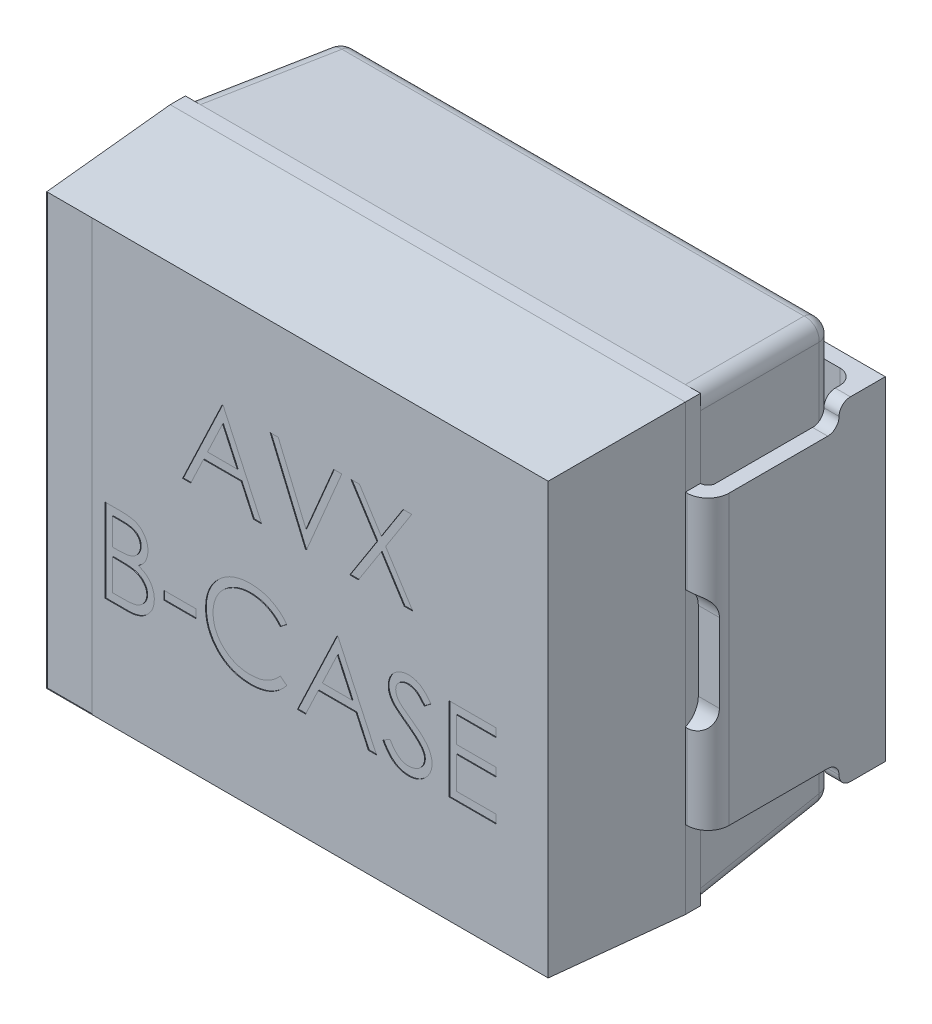
SolidWorks part; units mm, degrees
ref_plane "Front Plane" through (0, 0, 0) normal (0, 0, 1) x (1, 0, 0)
ref_plane "Top Plane" through (0, 0, 0) normal (0, 1, 0) x (1, 0, 0)
ref_plane "Right Plane" through (0, 0, 0) normal (1, 0, 0) x (0, 0, -1)
sketch "Sketch1" plane through (0, 0, 0) normal (0, 0, 1) x (1, 0, 0)
  line L1 (-1.7, -1.465) -> (-1.7, 1.465)
  line L2 (-1.7, -1.465) -> (1.7, -1.465)
  line L3 (1.7, -1.465) -> (1.7, 1.465)
  line L4 (-1.7, 1.465) -> (1.7, 1.465)
  dimension "D1" = 3.4
  dimension "D2" = 2.93
  dimension "D3" = 1.465
  dimension "D4" = 1.7
extrude "Boss-Extrude1" add sketch "Sketch1" along normal blind 0.95 from offset 0.12
ref_plane "Plane1" through (0, 0, 1.07) normal (0, 0, 1) x (1, 0, 0)
ref_plane "Plane2" through (0, 0, 1.17) normal (0, 0, 1) x (1, 0, 0)
sketch "Sketch2" plane through (0, 0, 1.07) normal (0, 0, 1) x (1, 0, 0)
  line L1 (-1.7, -1.465) -> (-1.7, 1.465)
  line L2 (-1.7, -1.465) -> (1.7, -1.465)
  line L3 (1.7, -1.465) -> (1.7, 1.465)
  line L4 (-1.7, 1.465) -> (1.7, 1.465)
  dimension "D1" = 1.7
  dimension "D2" = 2.93
  dimension "D3" = 1.465
  dimension "D4" = 3.4
sketch "Sketch3" plane through (0, 0, 1.17) normal (0, 0, 1) x (1, 0, 0)
  line L1 (-1.7, -1.465) -> (-1.7, 1.465)
  line L2 (-1.7, -1.465) -> (1.7, -1.465)
  line L3 (1.7, -1.465) -> (1.7, 1.465)
  line L4 (-1.7, 1.465) -> (1.7, 1.465)
  dimension "D1" = 1.465
  dimension "D2" = 2.93
  dimension "D3" = 1.7
  dimension "D4" = 3.4
chamfer "Chamfer3" distance 0.95 angle 5 4 edges at (0, -1.465, 0.12) (1.7, 0, 0.12) (0, 1.465, 0.12) (-1.7, 0, 0.12) first distance on face at (0, -1.465, 0.595) first distance on face at (1.7, 0, 0.595) first distance on face at (0, 1.465, 0.595) first distance on face at (-1.7, 0, 0.595)
fillet "Fillet4" radius 0.1 8 edges at (-1.6584, -1.4234, 0.595) (1.6584, -1.4234, 0.595) (1.6584, 1.4234, 0.595) (-1.6584, 1.4234, 0.595) (1.6169, 0, 0.12) (0, -1.3819, 0.12) (-1.6169, 0, 0.12) (0, 1.3819, 0.12)
extrude "Boss-Extrude2" add sketch "Sketch2" along normal blind 0.1
extrude "Boss-Extrude3" add sketch "Sketch3" along normal blind 0.86 draft 3
sketch "Sketch4" plane through (0, 0, 0) normal (0, 0, 1) x (1, 0, 0)
  line L1 (-0.7, -1.25) -> (-0.7, 1.25)
  line L2 (-0.7, -1.25) -> (0.7, -1.25)
  line L3 (0.7, -1.25) -> (0.7, 1.25)
  line L4 (-0.7, 1.25) -> (0.7, 1.25)
  dimension "D1" = 0.7
  dimension "D2" = 2.5
  dimension "D3" = 1.4
  dimension "D4" = 1.25
extrude "Boss-Extrude4" add sketch "Sketch4" along normal blind 0.1 from offset 0.02
fillet "Fillet5" radius 0.1 4 edges at (0, -1.25, 0.02) (0.7, 0, 0.02) (0, 1.25, 0.02) (-0.7, 0, 0.02)
sketch "Sketch6" plane through (0, 0, 0) normal (0, 1, 0) x (1, 0, 0)
  line L0 (-1.7, -1.17) -> (-1.7, -1.07)
  line L1 (-1.6116, -1.17) -> (1.6116, -1.17) construction
  line L2 (-1.6549, -2.03) -> (-1.7, -1.17) construction
  line L3 (-1.6116, -1.07) -> (1.6116, -1.07) construction
  line L4 (-1.7, -1.17) -> (-1.7, -1.07) construction
  line L5 (-1.7, -1.07) -> (-1.701, -1.07)
  line L6 (-1.75, -1.021) -> (-1.75, -0.2)
  line L7 (-1.65, -0.1) -> (-1.15, -0.1)
  line L8 (0, -0.02) -> (0, -2.03) construction
  line L9 (-1.15, -0.1) -> (-1.15, 0)
  line L10 (-1.15, 0) -> (-1.85, 0)
  line L11 (-1.85, 0) -> (-1.85, -1.03)
  line L12 (-1.71, -1.17) -> (-1.7, -1.17)
  line L13 (-0.6, -0.02) -> (0.6, -0.02) construction
  line L14 (1.6549, -2.03) -> (-1.6549, -2.03) construction
  line L15 (1.71, -1.17) -> (1.7, -1.17)
  line L16 (1.85, 0) -> (1.85, -1.03)
  line L17 (1.15, 0) -> (1.85, 0)
  line L18 (1.15, -0.1) -> (1.15, 0)
  line L19 (1.65, -0.1) -> (1.15, -0.1)
  line L20 (1.75, -1.021) -> (1.75, -0.2)
  line L21 (1.7, -1.07) -> (1.701, -1.07)
  line L22 (1.7, -1.17) -> (1.7, -1.07)
  arc A0 (-1.85, -1.03) -> (-1.71, -1.17) centre (-1.71, -1.03) ccw
  arc A1 (-1.701, -1.07) -> (-1.75, -1.021) centre (-1.701, -1.021) cw
  arc A2 (-1.75, -0.2) -> (-1.65, -0.1) centre (-1.65, -0.2) cw
  arc A3 (1.75, -0.2) -> (1.65, -0.1) centre (1.65, -0.2) ccw
  arc A4 (1.701, -1.07) -> (1.75, -1.021) centre (1.701, -1.021) ccw
  arc A5 (1.85, -1.03) -> (1.71, -1.17) centre (1.71, -1.03) cw
  point P15 (-1.85, -1.17)
  point P21 (-1.75, -1.07)
  point P24 (-1.75, -0.1)
  point P45 (1.75, -0.1)
  point P46 (1.75, -1.07)
  point P47 (1.85, -1.17)
  dimension "D6" = 0.14
  dimension "D7" = 0.049
  dimension "D8" = 0.1
  dimension "D1" = 0.97
  dimension "D2" = 0.15
  dimension "D3" = 0.1
  dimension "D4" = 0.1
  dimension "D5" = 0.7
extrude "Boss-Extrude5" add sketch "Sketch6" along normal mid plane 2.2
ref_plane "Plane3" through (-1.85, 0, 0) normal (-1, 0, 0) x (0, 0, 1)
sketch "Sketch7" plane through (-1.85, 0, 0) normal (-1, 0, 0) x (0, 0, 1)
  line L0 (0, 0) -> (2.03, 0) construction
  line L1 (2.03, 1.4199) -> (2.03, -1.4199) construction
  line L2 (1.17, 1.1) -> (1.17, -1.1) construction
  line L4 (1.17, 0.475) -> (0.559, 0.475)
  line L5 (1.17, 0.475) -> (1.17, -0.475)
  line L6 (1.17, -0.475) -> (0.559, -0.475)
  line L7 (0.459, 0.375) -> (0.459, -0.375)
  arc A0 (0.559, -0.475) -> (0.459, -0.375) centre (0.559, -0.375) cw
  arc A1 (0.559, 0.475) -> (0.459, 0.375) centre (0.559, 0.375) ccw
  point P16 (0.459, 0.475)
  dimension "D4" = 0.1
  dimension "D1" = 0.475
  dimension "D2" = 0.95
  dimension "D3" = 0.711
extrude "Cut-Extrude3" cut sketch "Sketch7" against normal blind 0.15
sketch "Sketch11" plane through (1.7, 0, -3.4788) normal (-1, 0, 0) x (0, 0, 1)
  line L0 (4.6488, -1.1) -> (3.7088, -1.1)
  line L1 (4.6488, -0.95) -> (4.6488, -1.1)
  line L2 (4.5088, 1.1) -> (3.4788, 1.1) construction
  line L3 (4.6488, 1.1) -> (4.6488, -1.1) construction
  line L4 (3.8588, -0.95) -> (4.6488, -0.95)
  line L14 (3.4788, 0) -> (4.6488, 0) construction
  line L16 (3.4788, 1.1) -> (3.4788, -1.1) construction
  line L18 (4.6477, 0.393) -> (4.6488, 0.3935)
  line L19 (4.5628, -0.2597) -> (4.5628, 0.2597)
  line L20 (4.6488, -0.3935) -> (4.6477, -0.393)
  line L21 (4.6488, 0.3935) -> (4.6488, -0.3935)
  line L22 (3.8588, 0.95) -> (4.6488, 0.95)
  line L23 (4.6488, 0.95) -> (4.6488, 1.1)
  line L24 (4.6488, 1.1) -> (3.7088, 1.1)
  arc A0 (3.7838, -1.025) -> (3.8588, -0.95) centre (3.8588, -1.025) cw
  arc A1 (3.7838, -1.025) -> (3.7088, -1.1) centre (3.7088, -1.025) cw
  arc A6 (4.5628, 0.2597) -> (4.6477, 0.393) centre (4.7098, 0.2597) cw
  arc A7 (4.6477, -0.393) -> (4.5628, -0.2597) centre (4.7098, -0.2597) cw
  arc A8 (3.7838, 1.025) -> (3.7088, 1.1) centre (3.7088, 1.025) ccw
  arc A9 (3.7838, 1.025) -> (3.8588, 0.95) centre (3.8588, 1.025) ccw
  dimension "D2" = 0.15
  dimension "D3" = 0.94
  dimension "D6" = 0.147
  dimension "D1" = 1.17
  dimension "D4" = 0.086
  dimension "D5" = 0.787
  dimension "D7" = 65
  dimension "D8" = 65
extrude "Cut-Extrude6" cut sketch "Sketch11" against normal blind 0.15
sketch "Sketch15" plane through (0, 0, 2.03) normal (0, 0, 1) x (1, 0, 0)
  line L0 (-1.6549, 0.23) -> (1.6549, 0.23) construction
  text T0 "AVX\r\nB-CASE" font "Century Gothic" height 0.55
extrude "Cut-Extrude7" cut sketch "Sketch15" against normal blind 0.005
sketch "Sketch16" plane through (0, 0, 2.03) normal (0, 0, 1) x (1, 0, 0)
  line L0 (-1.6549, -1.4199) -> (1.6549, -1.4199) construction
  line L1 (-1.6549, 1.4199) -> (-1.3549, 1.4199)
  line L2 (-1.6549, 1.4199) -> (-1.6549, -1.4199)
  line L3 (-1.6549, -1.4199) -> (-1.3549, -1.4199)
  line L4 (-1.3549, 1.4199) -> (-1.3549, -1.4199)
  dimension "D1" = 0.3
extrude "Cut-Extrude8" cut sketch "Sketch16" against normal blind 0.005
